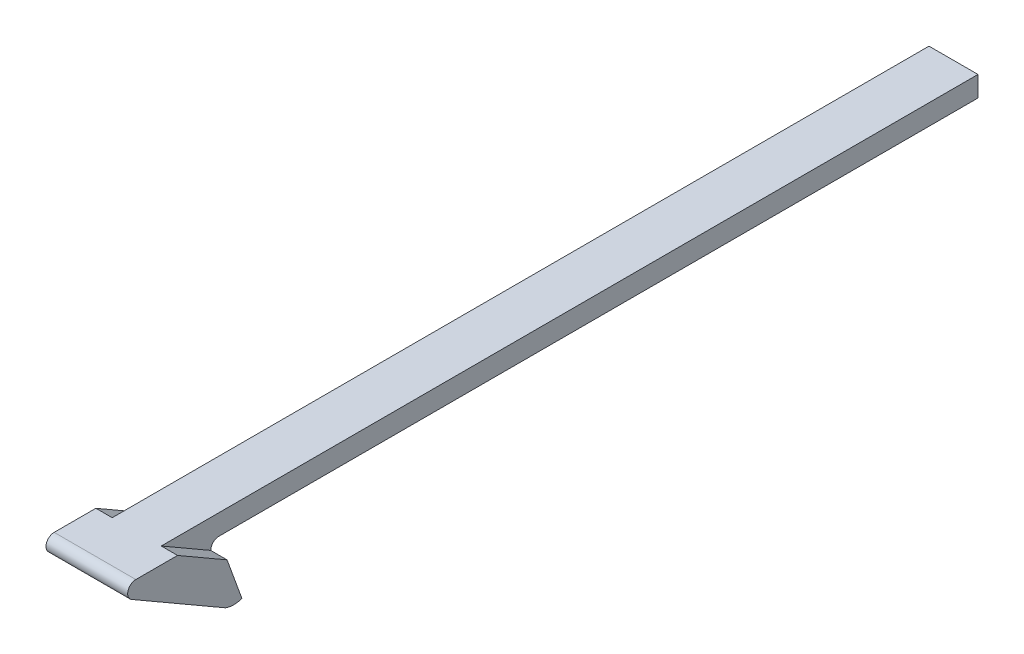
SolidWorks part; units mm, degrees
ref_plane "Front" through (0, 0, 0) normal (0, 0, 1) x (1, 0, 0)
ref_plane "Top" through (0, 0, 0) normal (0, 1, 0) x (1, 0, 0)
ref_plane "Right" through (0, 0, 0) normal (1, 0, 0) x (0, 0, -1)
ref_axis "X" through (-80.9, 0, 0) along (1, 0, 0)
ref_axis "Y" through (0, -50, 0) along (0, 1, 0)
ref_axis "Z" through (0, 0, -80.9) along (0, 0, 1)
sketch "Sketch1" plane through (0, 0, 0) normal (1, 0, 0) x (0, 0, -1)
  line L0 (0, 0) -> (0, -2.5)
  line L1 (0, -2.5) -> (100, -2.5)
  line L2 (100, -2.5) -> (100, 0)
  line L3 (100, 0) -> (0, 0)
  dimension "D1" = 2.5
  dimension "D2" = 100
extrude "Boss-Extrude1" add sketch "Sketch1" along normal mid plane 6
sketch "Sketch2" plane through (0, 0, 0) normal (1, 0, 0) x (0, 0, -1)
  line L0 (0, 0) -> (-8.8404, 0)
  line L2 (-8.8404, 0) -> (5.882, -8.5)
  line L6 (0, -2.5) -> (100, -2.5) construction
  line L7 (7.882, -8.5) -> (6.0622, -3.5)
  line L9 (0, 0) -> (6.0622, -3.5)
  arc A0 (5.882, -8.5) -> (7.882, -8.5) centre (6.882, -5.6716) ccw
  point P2 (0, 0)
  dimension "D3" = 3
  dimension "D1" = 30
  dimension "D2" = 6
  dimension "D4" = 1
  dimension "D5" = 20
  dimension "D6" = 2
extrude "Boss-Extrude2" add sketch "Sketch2" along normal mid plane 10
fillet "Fillet4" radius 1 1 edges at (0, -2.5, -4.3301)
fillet "Fillet2" radius 1 1 edges at (0, 0, 8.8404)
